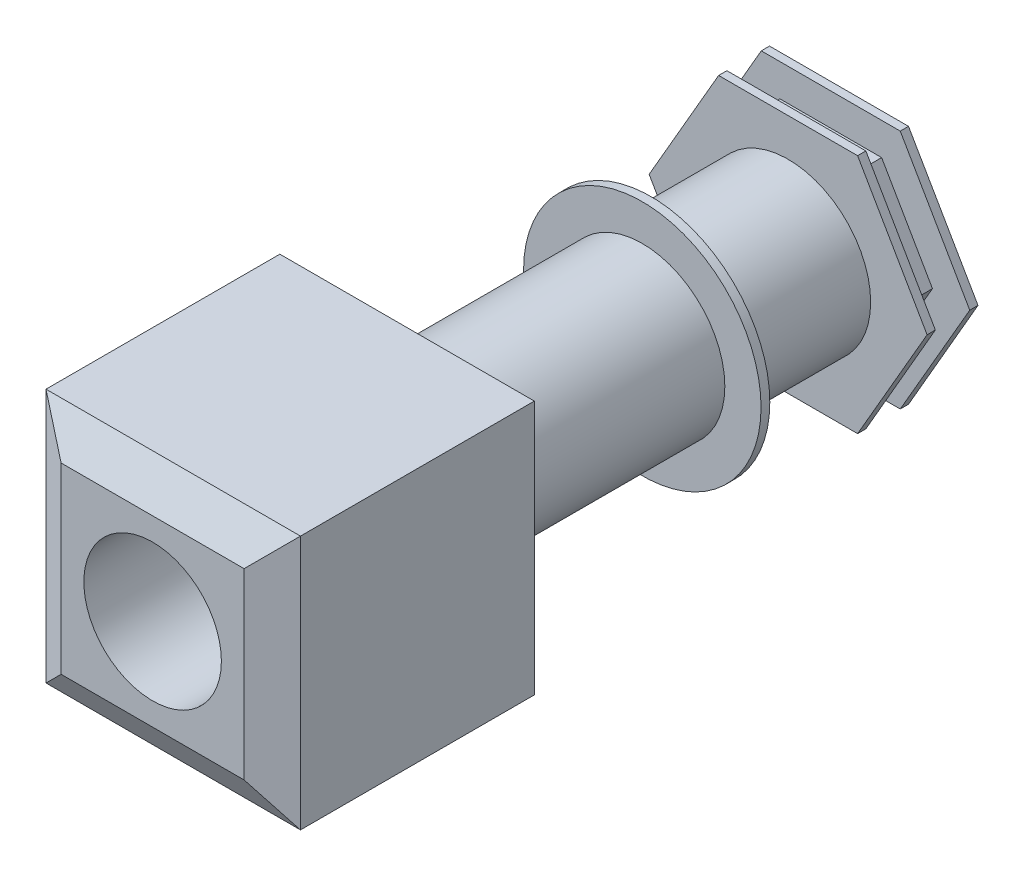
SolidWorks part; units mm, degrees
ref_plane "Front Plane" through (0, 0, 0) normal (0, 0, 1) x (1, 0, 0)
ref_plane "Top Plane" through (0, 0, 0) normal (0, 1, 0) x (1, 0, 0)
ref_plane "Right Plane" through (0, 0, 0) normal (1, 0, 0) x (0, 0, -1)
sketch "Sketch1" plane through (0, 0, 0) normal (0, 0, 1) x (1, 0, 0)
  line L1 (202.0726, 0) -> (101.0363, 175)
  line L2 (101.0363, 175) -> (-101.0363, 175)
  line L3 (-101.0363, 175) -> (-202.0726, 0)
  line L4 (-202.0726, 0) -> (-101.0363, -175)
  line L5 (-101.0363, -175) -> (101.0363, -175)
  line L6 (101.0363, -175) -> (202.0726, 0)
  circle A0 centre (0, 0) radius 175 construction
extrude "Boss-Extrude1" add sketch "Sketch1" along normal blind 12
sketch "Sketch2" plane through (0, 0, 12) normal (0, 0, 1) x (1, 0, 0)
  line L1 (147.8875, 0) -> (73.9437, 128.0743)
  line L2 (73.9437, 128.0743) -> (-73.9437, 128.0743)
  line L3 (-73.9437, 128.0743) -> (-147.8875, 0)
  line L4 (-147.8875, 0) -> (-73.9437, -128.0743)
  line L5 (-73.9437, -128.0743) -> (73.9437, -128.0743)
  line L6 (73.9437, -128.0743) -> (147.8875, 0)
  circle A0 centre (0, 0) radius 128.0743 construction
extrude "Boss-Extrude2" add sketch "Sketch2" along normal blind 50
sketch "Sketch3" plane through (0, 0, 62) normal (0, 0, 1) x (1, 0, 0)
  line L1 (202.0726, 0) -> (101.0363, 175)
  line L2 (101.0363, 175) -> (-101.0363, 175)
  line L3 (-101.0363, 175) -> (-202.0726, 0)
  line L4 (-202.0726, 0) -> (-101.0363, -175)
  line L5 (-101.0363, -175) -> (101.0363, -175)
  line L6 (101.0363, -175) -> (202.0726, 0)
  circle A0 centre (0, 0) radius 175 construction
extrude "Boss-Extrude3" add sketch "Sketch3" along normal blind 12
sketch "Sketch4" plane through (0, 0, 74) normal (0, 0, 1) x (1, 0, 0)
  circle A0 centre (0, 0) radius 120
extrude "Boss-Extrude4" add sketch "Sketch4" along normal blind 200
sketch "Sketch5" plane through (0, 0, 274) normal (0, 0, 1) x (1, 0, 0)
  circle A0 centre (0, 0) radius 172.6469
extrude "Boss-Extrude5" add sketch "Sketch5" along normal blind 12
chamfer "Chamfer1" distance 10 angle 80 1 edges at (120, 0, 274) first distance on face at (120, 0, 274)
sketch "Sketch6" plane through (0, 0, 286) normal (0, 0, 1) x (1, 0, 0)
  circle A0 centre (0, 0) radius 120
extrude "Boss-Extrude6" add sketch "Sketch6" along normal blind 330
sketch "Sketch8" plane through (0, 0, 616) normal (0, 0, 1) x (1, 0, 0)
  circle A0 centre (0, 0) radius 172.6469
extrude "Boss-Extrude7" add sketch "Sketch8" along normal blind 12
chamfer "Chamfer2" distance 6 angle 70 1 edges at (120, 0, 616) first distance on face at (120, 0, 616)
sketch "Sketch9" plane through (0, 0, 628) normal (0, 0, 1) x (1, 0, 0)
  line L1 (-185, 185) -> (185, 185)
  line L2 (-185, 185) -> (-185, -185)
  line L3 (-185, -185) -> (185, -185)
  line L4 (185, 185) -> (185, -185)
  line L5 (-185, 185) -> (185, -185) construction
  line L6 (-185, -185) -> (185, 185) construction
  point P0 (0, 0)
extrude "Boss-Extrude8" add sketch "Sketch9" along normal blind 370
sketch "Sketch10" plane through (0, 0, 998) normal (0, 0, 1) x (1, 0, 0)
  circle A0 centre (0, 0) radius 100
extrude "Cut-Extrude1" cut sketch "Sketch10" against normal blind 900
chamfer "Chamfer3" distance 30 angle 60 4 edges at (185, 0, 998) (0, -185, 998) (-185, 0, 998) (0, 185, 998) first distance on face at (185, 0, 813) first distance on face at (0, -185, 813) first distance on face at (-185, 0, 813) first distance on face at (0, 185, 813)
